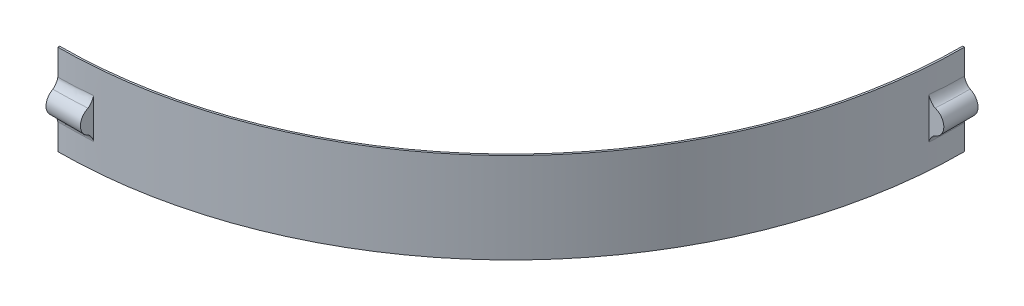
SolidWorks part; units mm, degrees
ref_plane "Front Plane" through (0, 0, 0) normal (0, 0, 1) x (1, 0, 0)
ref_plane "Top Plane" through (0, 0, 0) normal (0, 1, 0) x (1, 0, 0)
ref_plane "Right Plane" through (0, 0, 0) normal (1, 0, 0) x (0, 0, -1)
sketch "Sketch1" plane through (0, 0, 0) normal (0, 0, 1) x (1, 0, 0)
  line L0 (0, 3.3639) -> (0, -36.2756) construction
  line L1 (127.254, 12.7) -> (126.746, 12.7)
  line L2 (127.254, 12.7) -> (127.254, -12.7)
  line L3 (127.254, -12.7) -> (126.746, -12.7)
  line L4 (126.746, 12.7) -> (126.746, -12.7)
  line L5 (127.254, 12.7) -> (126.746, -12.7) construction
  line L6 (127.254, -12.7) -> (126.746, 12.7) construction
  point P0 (127, 0)
  dimension "D1" = 25.4
  dimension "D2" = 0.508
  dimension "D3" = 127
revolve "Revolve1" add sketch "Sketch1" angle 90 about L0
sketch "Sketch4" plane through (0, 0, 0) normal (-1, 0, 0) x (0, 0, 1)
  line L0 (126.746, 12.7) -> (126.746, -12.7) construction
  circle A0 centre (127, 0) radius 3.556
  point P2 (126.746, 0)
  dimension "D2" = 7.112
  dimension "D1" = 0.254
extrude "Boss-Extrude1" add sketch "Sketch4" against normal blind 9.652
sketch "Sketch6" plane through (9.652, 0, 0) normal (1, 0, 0) x (0, 0, -1)
  circle A0 centre (-127, 0) radius 3.175
  circle A2 centre (-127, 0) radius 3.556 construction
  dimension "D1" = 6.35
fillet "Fillet6" radius 2.54 2 edges at (7.112, 3.5556, 127.0551) (2.5454, -3.5486, 127.2285)
fillet "Fillet8" radius 2.54 2 edges at (7.112, -3.5269, 126.5463) (2.5454, 3.545, 126.7204)
sketch "Sketch7" plane through (0, 0, 0) normal (0, 0, -1) x (-1, 0, 0)
  line L0 (-127.254, -12.7) -> (-127.254, 12.7) construction
  circle A0 centre (-127.508, 0) radius 3.556
  point P2 (-127.254, 0)
  dimension "D1" = 7.112
  dimension "D2" = 0.254
extrude "Boss-Extrude2" add sketch "Sketch7" against normal blind 9.6012
sketch "Sketch8" plane through (0, 0, 9.6012) normal (0, 0, 1) x (1, 0, 0)
  circle A0 centre (127.508, 0) radius 3.175
  circle A1 centre (127.508, 0) radius 3.556 construction
  dimension "D1" = 6.35
fillet "Fillet11" radius 2.54 4 edges at (126.5463, 3.4235, 7.112) (126.7214, -3.4679, 2.4946) (127.0551, -3.527, 7.112) (127.2296, 3.5451, 2.4944)
sketch "Sketch9" plane through (0, 0, 0) normal (-1, 0, 0) x (0, 0, 1)
  circle A0 centre (127, 0) radius 3.175
  dimension "D1" = 6.35
extrude "Cut-Extrude1" cut sketch "Sketch9" against normal blind 9.525
sketch "Sketch10" plane through (0, 0, 0) normal (0, 0, -1) x (-1, 0, 0)
  circle A0 centre (-127.508, 0) radius 3.175
extrude "Cut-Extrude2" cut sketch "Sketch10" against normal blind 9.525
